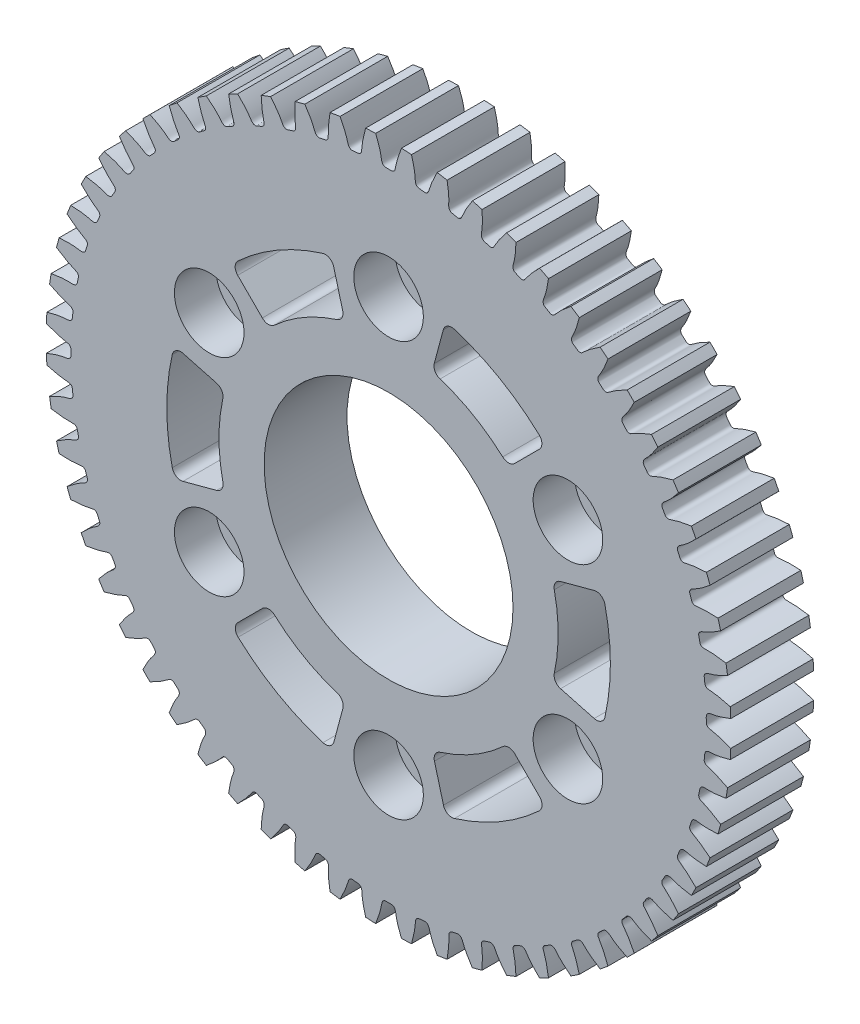
SolidWorks part; units mm, degrees
material "7075-T6 (SN)"
ref_plane "Front Plane" through (0, 0, 0) normal (0, 0, 1) x (1, 0, 0)
ref_plane "Top Plane" through (0, 0, 0) normal (0, 1, 0) x (1, 0, 0)
ref_plane "Right Plane" through (0, 0, 0) normal (1, 0, 0) x (0, 0, -1)
ref_plane "Plane1" through (0, 0, 4.7625) normal (0, 0, 1) x (1, 0, 0)
sketch "Sketch1" plane through (0, 0, 4.7625) normal (0, 0, 1) x (1, 0, 0)
  arc A0 (39.3421, 1.4811) -> (39.2814, 2.6394) centre (0, 0) ccw
  arc A1 (38.9718, 5.5854) -> (38.7904, 6.7309) centre (0, 0) ccw
  arc A2 (38.1745, 9.6285) -> (37.8743, 10.7487) centre (0, 0) ccw
  arc A3 (36.9589, 13.566) -> (36.5433, 14.6488) centre (0, 0) ccw
  arc A4 (35.3384, 17.355) -> (34.8118, 18.3884) centre (0, 0) ccw
  arc A5 (33.3307, 20.9538) -> (32.699, 21.9265) centre (0, 0) ccw
  arc A6 (30.9579, 24.323) -> (30.228, 25.2243) centre (0, 0) ccw
  arc A7 (28.2458, 27.4257) -> (27.4257, 28.2458) centre (0, 0) ccw
  arc A8 (25.2243, 30.228) -> (24.323, 30.9579) centre (0, 0) ccw
  arc A9 (21.9265, 32.699) -> (20.9538, 33.3307) centre (0, 0) ccw
  arc A10 (18.3884, 34.8118) -> (17.355, 35.3384) centre (0, 0) ccw
  arc A11 (14.6488, 36.5433) -> (13.566, 36.9589) centre (0, 0) ccw
  arc A12 (10.7487, 37.8743) -> (9.6285, 38.1745) centre (0, 0) ccw
  arc A13 (6.7309, 38.7904) -> (5.5854, 38.9718) centre (0, 0) ccw
  arc A14 (2.6394, 39.2814) -> (1.4811, 39.3421) centre (0, 0) ccw
  arc A15 (-1.4811, 39.3421) -> (-2.6394, 39.2814) centre (0, 0) ccw
  arc A16 (-5.5854, 38.9718) -> (-6.7309, 38.7904) centre (0, 0) ccw
  arc A17 (-9.6285, 38.1745) -> (-10.7487, 37.8743) centre (0, 0) ccw
  arc A18 (-13.566, 36.9589) -> (-14.6488, 36.5433) centre (0, 0) ccw
  arc A19 (-17.355, 35.3384) -> (-18.3884, 34.8118) centre (0, 0) ccw
  arc A20 (-20.9538, 33.3307) -> (-21.9265, 32.699) centre (0, 0) ccw
  arc A21 (-24.323, 30.9579) -> (-25.2243, 30.228) centre (0, 0) ccw
  arc A22 (-27.4257, 28.2458) -> (-28.2458, 27.4257) centre (0, 0) ccw
  arc A23 (-30.228, 25.2243) -> (-30.9579, 24.323) centre (0, 0) ccw
  arc A24 (-32.699, 21.9265) -> (-33.3307, 20.9538) centre (0, 0) ccw
  arc A25 (-34.8118, 18.3884) -> (-35.3384, 17.355) centre (0, 0) ccw
  arc A26 (-36.5433, 14.6488) -> (-36.9589, 13.566) centre (0, 0) ccw
  arc A27 (-37.8743, 10.7487) -> (-38.1745, 9.6285) centre (0, 0) ccw
  arc A28 (-38.7904, 6.7309) -> (-38.9718, 5.5854) centre (0, 0) ccw
  arc A29 (-39.2814, 2.6394) -> (-39.3421, 1.4811) centre (0, 0) ccw
  arc A30 (-39.3421, -1.4811) -> (-39.2814, -2.6394) centre (0, 0) ccw
  arc A31 (-38.9718, -5.5854) -> (-38.7904, -6.7309) centre (0, 0) ccw
  arc A32 (-38.1745, -9.6285) -> (-37.8743, -10.7487) centre (0, 0) ccw
  arc A33 (-36.9589, -13.566) -> (-36.5433, -14.6488) centre (0, 0) ccw
  arc A34 (-35.3384, -17.355) -> (-34.8118, -18.3884) centre (0, 0) ccw
  arc A35 (-33.3307, -20.9538) -> (-32.699, -21.9265) centre (0, 0) ccw
  arc A36 (-30.9579, -24.323) -> (-30.228, -25.2243) centre (0, 0) ccw
  arc A37 (-28.2458, -27.4257) -> (-27.4257, -28.2458) centre (0, 0) ccw
  arc A38 (-25.2243, -30.228) -> (-24.323, -30.9579) centre (0, 0) ccw
  arc A39 (-21.9265, -32.699) -> (-20.9538, -33.3307) centre (0, 0) ccw
  arc A40 (-18.3884, -34.8118) -> (-17.355, -35.3384) centre (0, 0) ccw
  arc A41 (-14.6488, -36.5433) -> (-13.566, -36.9589) centre (0, 0) ccw
  arc A42 (-10.7487, -37.8743) -> (-9.6285, -38.1745) centre (0, 0) ccw
  arc A43 (-6.7309, -38.7904) -> (-5.5854, -38.9718) centre (0, 0) ccw
  arc A44 (-2.6394, -39.2814) -> (-1.4811, -39.3421) centre (0, 0) ccw
  arc A45 (1.4811, -39.3421) -> (2.6394, -39.2814) centre (0, 0) ccw
  arc A46 (5.5854, -38.9718) -> (6.7309, -38.7904) centre (0, 0) ccw
  arc A47 (9.6285, -38.1745) -> (10.7487, -37.8743) centre (0, 0) ccw
  arc A48 (13.566, -36.9589) -> (14.6488, -36.5433) centre (0, 0) ccw
  arc A49 (17.355, -35.3384) -> (18.3884, -34.8118) centre (0, 0) ccw
  arc A50 (20.9538, -33.3307) -> (21.9265, -32.699) centre (0, 0) ccw
  arc A51 (24.323, -30.9579) -> (25.2243, -30.228) centre (0, 0) ccw
  arc A52 (27.4257, -28.2458) -> (28.2458, -27.4257) centre (0, 0) ccw
  arc A53 (30.228, -25.2243) -> (30.9579, -24.323) centre (0, 0) ccw
  arc A54 (32.699, -21.9265) -> (33.3307, -20.9538) centre (0, 0) ccw
  arc A55 (34.8118, -18.3884) -> (35.3384, -17.355) centre (0, 0) ccw
  arc A56 (36.5433, -14.6488) -> (36.9589, -13.566) centre (0, 0) ccw
  arc A57 (37.8743, -10.7487) -> (38.1745, -9.6285) centre (0, 0) ccw
  arc A58 (38.7904, -6.7309) -> (38.9718, -5.5854) centre (0, 0) ccw
  arc A59 (39.2814, -2.6394) -> (39.3421, -1.4811) centre (0, 0) ccw
  spline S0 degree 3 number of poles 79 (39.3421, 1.4811) -> (39.3421, -1.4811)
  spline S1 degree 3 number of poles 79 (38.9718, 5.5854) -> (39.2814, 2.6394)
  spline S2 degree 3 number of poles 79 (38.1745, 9.6285) -> (38.7904, 6.7309)
  spline S3 degree 3 number of poles 79 (36.9589, 13.566) -> (37.8743, 10.7487)
  spline S4 degree 3 number of poles 79 (35.3384, 17.355) -> (36.5433, 14.6488)
  spline S5 degree 3 number of poles 79 (33.3307, 20.9538) -> (34.8118, 18.3884)
  spline S6 degree 3 number of poles 79 (30.9579, 24.323) -> (32.699, 21.9265)
  spline S7 degree 3 number of poles 79 (28.2458, 27.4257) -> (30.228, 25.2243)
  spline S8 degree 3 number of poles 79 (25.2243, 30.228) -> (27.4257, 28.2458)
  spline S9 degree 3 number of poles 79 (21.9265, 32.699) -> (24.323, 30.9579)
  spline S10 degree 3 number of poles 79 (18.3884, 34.8118) -> (20.9538, 33.3307)
  spline S11 degree 3 number of poles 79 (14.6488, 36.5433) -> (17.355, 35.3384)
  spline S12 degree 3 number of poles 79 (10.7487, 37.8743) -> (13.566, 36.9589)
  spline S13 degree 3 number of poles 79 (6.7309, 38.7904) -> (9.6285, 38.1745)
  spline S14 degree 3 number of poles 79 (2.6394, 39.2814) -> (5.5854, 38.9718)
  spline S15 degree 3 number of poles 79 (-1.4811, 39.3421) -> (1.4811, 39.3421)
  spline S16 degree 3 number of poles 79 (-5.5854, 38.9718) -> (-2.6394, 39.2814)
  spline S17 degree 3 number of poles 79 (-9.6285, 38.1745) -> (-6.7309, 38.7904)
  spline S18 degree 3 number of poles 79 (-13.566, 36.9589) -> (-10.7487, 37.8743)
  spline S19 degree 3 number of poles 79 (-17.355, 35.3384) -> (-14.6488, 36.5433)
  spline S20 degree 3 number of poles 79 (-20.9538, 33.3307) -> (-18.3884, 34.8118)
  spline S21 degree 3 number of poles 79 (-24.323, 30.9579) -> (-21.9265, 32.699)
  spline S22 degree 3 number of poles 79 (-27.4257, 28.2458) -> (-25.2243, 30.228)
  spline S23 degree 3 number of poles 79 (-30.228, 25.2243) -> (-28.2458, 27.4257)
  spline S24 degree 3 number of poles 79 (-32.699, 21.9265) -> (-30.9579, 24.323)
  spline S25 degree 3 number of poles 79 (-34.8118, 18.3884) -> (-33.3307, 20.9538)
  spline S26 degree 3 number of poles 79 (-36.5433, 14.6488) -> (-35.3384, 17.355)
  spline S27 degree 3 number of poles 79 (-37.8743, 10.7487) -> (-36.9589, 13.566)
  spline S28 degree 3 number of poles 79 (-38.7904, 6.7309) -> (-38.1745, 9.6285)
  spline S29 degree 3 number of poles 79 (-39.2814, 2.6394) -> (-38.9718, 5.5854)
  spline S30 degree 3 number of poles 79 (-39.3421, -1.4811) -> (-39.3421, 1.4811)
  spline S31 degree 3 number of poles 79 (-38.9718, -5.5854) -> (-39.2814, -2.6394)
  spline S32 degree 3 number of poles 79 (-38.1745, -9.6285) -> (-38.7904, -6.7309)
  spline S33 degree 3 number of poles 79 (-36.9589, -13.566) -> (-37.8743, -10.7487)
  spline S34 degree 3 number of poles 79 (-35.3384, -17.355) -> (-36.5433, -14.6488)
  spline S35 degree 3 number of poles 79 (-33.3307, -20.9538) -> (-34.8118, -18.3884)
  spline S36 degree 3 number of poles 79 (-30.9579, -24.323) -> (-32.699, -21.9265)
  spline S37 degree 3 number of poles 79 (-28.2458, -27.4257) -> (-30.228, -25.2243)
  spline S38 degree 3 number of poles 79 (-25.2243, -30.228) -> (-27.4257, -28.2458)
  spline S39 degree 3 number of poles 79 (-21.9265, -32.699) -> (-24.323, -30.9579)
  spline S40 degree 3 number of poles 79 (-18.3884, -34.8118) -> (-20.9538, -33.3307)
  spline S41 degree 3 number of poles 79 (-14.6488, -36.5433) -> (-17.355, -35.3384)
  spline S42 degree 3 number of poles 79 (-10.7487, -37.8743) -> (-13.566, -36.9589)
  spline S43 degree 3 number of poles 79 (-6.7309, -38.7904) -> (-9.6285, -38.1745)
  spline S44 degree 3 number of poles 79 (-2.6394, -39.2814) -> (-5.5854, -38.9718)
  spline S45 degree 3 number of poles 79 (1.4811, -39.3421) -> (-1.4811, -39.3421)
  spline S46 degree 3 number of poles 79 (5.5854, -38.9718) -> (2.6394, -39.2814)
  spline S47 degree 3 number of poles 79 (9.6285, -38.1745) -> (6.7309, -38.7904)
  spline S48 degree 3 number of poles 79 (13.566, -36.9589) -> (10.7487, -37.8743)
  spline S49 degree 3 number of poles 79 (17.355, -35.3384) -> (14.6488, -36.5433)
  spline S50 degree 3 number of poles 79 (20.9538, -33.3307) -> (18.3884, -34.8118)
  spline S51 degree 3 number of poles 79 (24.323, -30.9579) -> (21.9265, -32.699)
  spline S52 degree 3 number of poles 79 (27.4257, -28.2458) -> (25.2243, -30.228)
  spline S53 degree 3 number of poles 79 (30.228, -25.2243) -> (28.2458, -27.4257)
  spline S54 degree 3 number of poles 79 (32.699, -21.9265) -> (30.9579, -24.323)
  spline S55 degree 3 number of poles 79 (34.8118, -18.3884) -> (33.3307, -20.9538)
  spline S56 degree 3 number of poles 79 (36.5433, -14.6488) -> (35.3384, -17.355)
  spline S57 degree 3 number of poles 79 (37.8743, -10.7487) -> (36.9589, -13.566)
  spline S58 degree 3 number of poles 79 (38.7904, -6.7309) -> (38.1745, -9.6285)
  spline S59 degree 3 number of poles 79 (39.2814, -2.6394) -> (38.9718, -5.5854)
extrude "Boss-Extrude1" add sketch "Sketch1" against normal blind 9.525
sketch "Sketch2" plane through (0, 0, 4.7625) normal (0, 0, 1) x (1, 0, 0)
  line L0 (-13.8065, -13.7706) -> (-18.0492, -18.0133)
  line L1 (-6.5508, -24.6442) -> (-4.9979, -18.8486)
  arc A0 (-18.0492, -18.0133) -> (-6.5508, -24.6442) centre (0, 0) ccw
  arc A1 (-4.9979, -18.8486) -> (-13.8065, -13.7706) centre (0, 0) cw
extrude "Cut-Extrude1" cut sketch "Sketch2" against normal through all
sketch "Sketch3" plane through (0, 0, 4.7625) normal (0, 0, 1) x (1, 0, 0)
  line L0 (-18.829, 5.0715) -> (-24.6245, 6.6244)
  line L1 (-24.6179, -6.6489) -> (-18.8223, -5.096)
  arc A0 (-24.6245, 6.6244) -> (-24.6179, -6.6489) centre (0, 0) ccw
  arc A1 (-18.8223, -5.096) -> (-18.829, 5.0715) centre (0, 0) cw
extrude "Cut-Extrude2" cut sketch "Sketch3" against normal through all
sketch "Sketch4" plane through (0, 0, 4.7625) normal (0, 0, 1) x (1, 0, 0)
  line L0 (-5.0224, 18.8421) -> (-6.5753, 24.6377)
  line L1 (-18.0671, 17.9953) -> (-13.8245, 13.7526)
  arc A0 (-6.5753, 24.6377) -> (-18.0671, 17.9953) centre (0, 0) ccw
  arc A1 (-13.8245, 13.7526) -> (-5.0224, 18.8421) centre (0, 0) cw
extrude "Cut-Extrude3" cut sketch "Sketch4" against normal through all
sketch "Sketch5" plane through (0, 0, 4.7625) normal (0, 0, 1) x (1, 0, 0)
  line L0 (13.8065, 13.7706) -> (18.0492, 18.0133)
  line L1 (6.5508, 24.6442) -> (4.9979, 18.8486)
  arc A0 (18.0492, 18.0133) -> (6.5508, 24.6442) centre (0, 0) ccw
  arc A1 (4.9979, 18.8486) -> (13.8065, 13.7706) centre (0, 0) cw
extrude "Cut-Extrude4" cut sketch "Sketch5" against normal through all
sketch "Sketch6" plane through (0, 0, 4.7625) normal (0, 0, 1) x (1, 0, 0)
  line L0 (18.829, -5.0715) -> (24.6245, -6.6244)
  line L1 (24.6179, 6.6489) -> (18.8223, 5.096)
  arc A0 (24.6245, -6.6244) -> (24.6179, 6.6489) centre (0, 0) ccw
  arc A1 (18.8223, 5.096) -> (18.829, -5.0715) centre (0, 0) cw
extrude "Cut-Extrude5" cut sketch "Sketch6" against normal through all
sketch "Sketch7" plane through (0, 0, -4.7625) normal (0, 0, -1) x (-1, 0, 0)
  line L0 (-6.5753, -24.6377) -> (-5.0224, -18.8421)
  line L1 (-13.8245, -13.7526) -> (-18.0671, -17.9953)
  arc A0 (-18.0671, -17.9953) -> (-6.5753, -24.6377) centre (0, 0) ccw
  arc A1 (-5.0224, -18.8421) -> (-13.8245, -13.7526) centre (0, 0) cw
extrude "Cut-Extrude6" cut sketch "Sketch7" against normal through all
hole_wizard "M25 Clearance Hole1" positions "Sketch9" profile "Sketch8" hole size "M25" standard "ANSI Metric"
sketch "Sketch9" plane through (0, 0, 4.7625) normal (0, 0, 1) x (1, 0, 0)
  point P0 (0, 0)
sketch "Sketch8" plane through (0, 0, 4.7625) normal (1, 0, 0) x (0, -1, 0)
  line L0 (0, 0) -> (0, 9.525)
  line L1 (0, 9.525) -> (14.3065, 9.525)
  line L2 (14.3065, 9.525) -> (14.3065, 0)
  line L5 (14.3065, 0) -> (0, 0)
  line L11 (0, -6.35) -> (0, 107.95) construction
  dimension "Thru Hole Dia." = 28.6131
  dimension "Thru Hole Depth" = 9.525
hole_wizard "CBORE for M4 Hex Head Machine Screw1" positions "Sketch11" profile "Sketch10" counterbore size "M4" standard "ANSI Metric"
sketch "Sketch11" plane through (0, 0, 4.7625) normal (0, 0, 1) x (1, 0, 0)
  point P0 (-20.6222, -11.9062)
  point P1 (0, 23.8125)
  point P2 (20.6222, -11.9063)
  point P3 (20.6222, 11.9062)
  point P4 (-20.6222, 11.9063)
  point P5 (0, -23.8125)
sketch "Sketch10" plane through (-20.6222, -11.9062, 4.7625) normal (1, 0, 0) x (0, -1, 0)
  line L0 (0, 0) -> (0, 9.525)
  line L1 (0, 9.525) -> (2.15, 9.525)
  line L3 (2.15, 9.525) -> (2.15, 4.7625)
  line L4 (2.15, 4.7625) -> (4, 4.7625)
  line L5 (4, 4.7625) -> (4, 0)
  line L7 (4, 0) -> (0, 0)
  line L11 (0, -6.35) -> (0, 107.95) construction
  dimension "Thru Hole Dia." = 4.3
  dimension "Thru Hole Depth" = 9.525
  dimension "C'Bore Dia." = 8
  dimension "C'Bore Depth" = 4.7625
fillet "Fillet1" radius 1 24 edges at (-13.8245, 13.7526, 0) (-4.9979, -18.8486, 0) (-18.8223, -5.096, 0) (5.0224, -18.8421, 0) (-5.0224, 18.8421, 0) (18.0671, -17.9953, 0) (-18.829, 5.0715, 0) (13.8245, -13.7526, 0) (-13.8065, -13.7706, 0) (24.6245, -6.6244, 0) (-6.5753, 24.6377, 0) (18.829, -5.0715, 0) (-18.0671, 17.9953, 0) (24.6179, 6.6489, 0) (-24.6245, 6.6244, 0) (18.8223, 5.096, 0) (-24.6179, -6.6489, 0) (18.0492, 18.0133, 0) (-18.0492, -18.0133, 0) (13.8065, 13.7706, 0) (-6.5508, -24.6442, 0) (6.5508, 24.6442, 0) (6.5753, -24.6377, 0) (4.9979, 18.8486, 0) tangent propagation no
